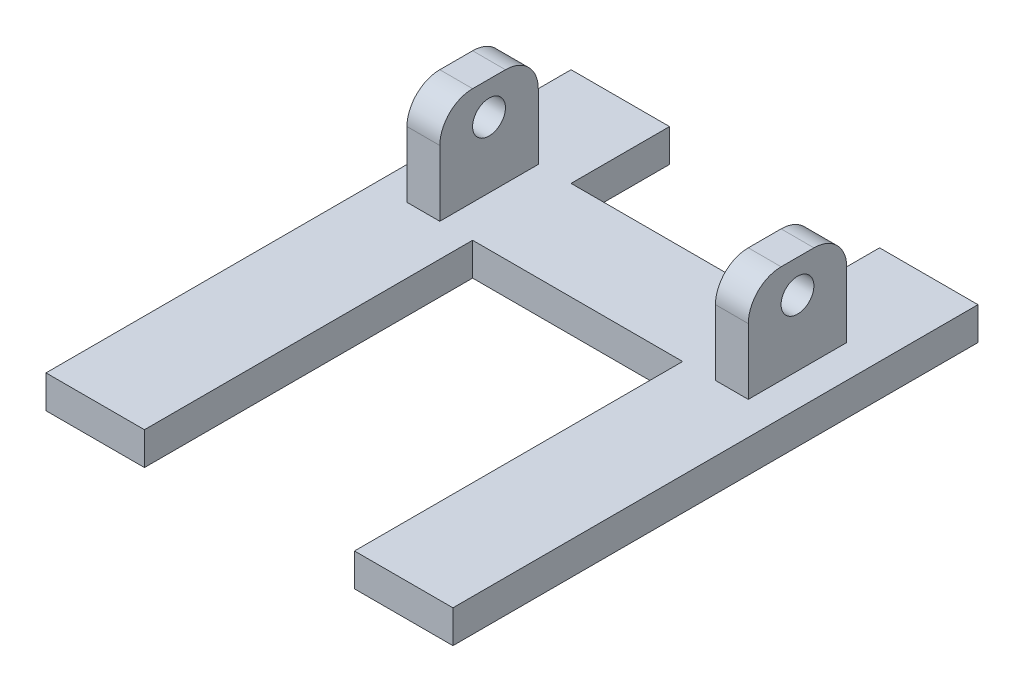
SolidWorks part; units mm, degrees
ref_plane "Front Plane" through (0, 0, 0) normal (0, 0, 1) x (1, 0, 0)
ref_plane "Top Plane" through (0, 0, 0) normal (0, 1, 0) x (1, 0, 0)
ref_plane "Right Plane" through (0, 0, 0) normal (1, 0, 0) x (0, 0, -1)
sketch "Sketch1" plane through (0, 0, 0) normal (0, 1, 0) x (1, 0, 0)
  line L0 (0, 0) -> (0, 80)
  line L1 (0, 80) -> (15, 80)
  line L2 (15, 80) -> (15, 0)
  line L3 (15, 0) -> (0, 0)
  line L4 (47, 80) -> (47, 0)
  line L5 (47, 0) -> (62, 0)
  line L6 (62, 0) -> (62, 80)
  line L7 (62, 80) -> (47, 80)
  line L8 (15, 50) -> (47, 50)
  line L9 (15, 65) -> (47, 65)
  line L10 (15, 65) -> (15, 50)
  line L11 (47, 65) -> (47, 50)
  point P11 (0, 0)
  point P12 (0, 0)
  point P13 (0, 0)
  dimension "D1" = 15
  dimension "D2" = 80
  dimension "D3" = 62
  dimension "D5" = 50
  dimension "D4" = 15
extrude "Boss-Extrude1" add sketch "Sketch1" along normal mid plane 5 contours L3 L2 L1 L0 | L9 L2 L8 L4 | L6 L7 L4 L5 region at (7.5, 0, -40) region at (31, 0, -57.5) region at (54.5, 0, -40)
sketch "Sketch2" plane through (0, 2.5, 0) normal (0, 1, 0) x (1, 0, 0)
  line L0 (31, 65) -> (31, 50) construction
  line L1 (15, 65) -> (47, 65) construction
  line L2 (15, 50) -> (47, 50) construction
  line L3 (52, 65) -> (52, 50)
  line L4 (52, 50) -> (57, 50)
  line L5 (57, 50) -> (57, 65)
  line L6 (57, 65) -> (52, 65)
  line L7 (5, 65) -> (5, 50)
  line L8 (5, 50) -> (10, 50)
  line L9 (10, 50) -> (10, 65)
  line L10 (10, 65) -> (5, 65)
  line L11 (10, 65) -> (52, 65) construction
  point P12 (31, 65)
  dimension "D1" = 5
  dimension "D2" = 42
extrude "Boss-Extrude2" add sketch "Sketch2" along normal blind 15
sketch "Sketch3" plane through (5, 0, 0) normal (-1, 0, 0) x (0, 0, 1)
  line L0 (-65, 17.5) -> (-50, 17.5) construction
  circle A0 centre (-57.5, 12.5) radius 2.5
  point P2 (0, 0)
  point P5 (-57.5, 17.5)
  dimension "D2" = 5
  dimension "D1" = 5
extrude "Cut-Extrude1" cut sketch "Sketch3" against normal up to surface (52 mm away) up to face at (57, 10, -57.5)
fillet "Fillet2" radius 5 4 edges at (54.5, 17.5, -50) (54.5, 17.5, -65) (7.5, 17.5, -65) (7.5, 17.5, -50)
